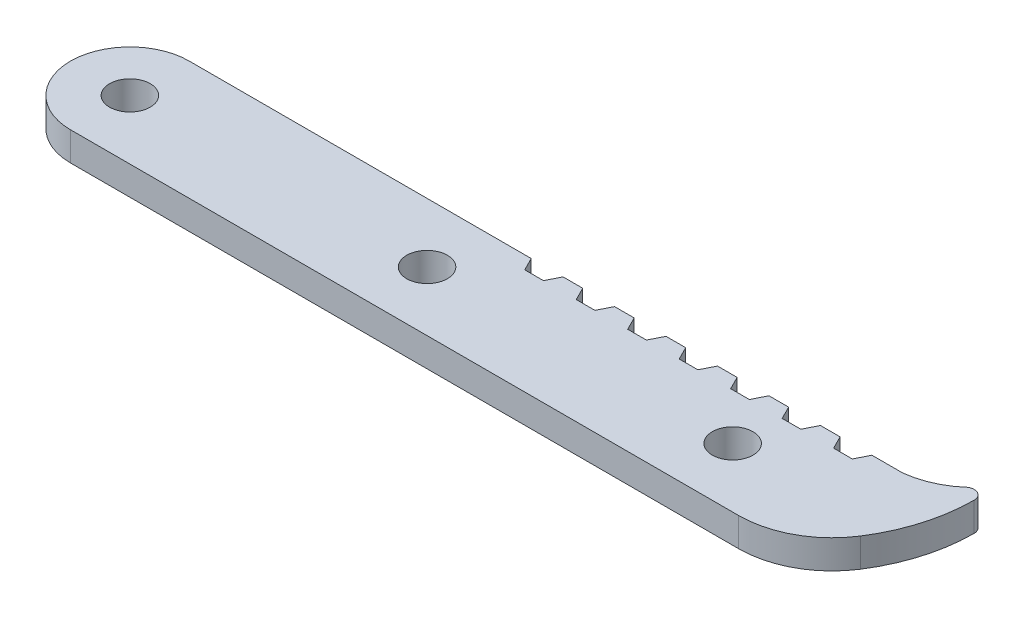
SolidWorks part; units mm, degrees
material "PET"
ref_plane "Front" through (0, 0, 0) normal (0, 0, 1) x (1, 0, 0)
ref_plane "Top" through (0, 0, 0) normal (0, 1, 0) x (1, 0, 0)
ref_plane "Right" through (0, 0, 0) normal (1, 0, 0) x (0, 0, -1)
sketch "Sketch1" plane through (0, 0, 0) normal (0, 1, 0) x (1, 0, 0)
  line L1 (-62.8447, 8.7002) -> (13.3553, 8.7002)
  line L3 (-62.8447, -3.9998) -> (13.3553, -3.9998)
  line L5 (-62.8447, 8.7002) -> (13.3553, -3.9998) construction
  line L6 (-62.8447, -3.9998) -> (13.3553, 8.7002) construction
  arc A0 (-62.8447, 8.7002) -> (-62.8447, -3.9998) centre (-62.8447, 2.3502) ccw
  arc A2 (13.3553, 8.7002) -> (13.3553, -3.9998) centre (13.3553, 2.3502) cw
  point P4 (-24.7447, 2.3502)
  dimension "D1" = 76.2
  dimension "D2" = 12.7
extrude "Boss-Extrude1" add sketch "Sketch1" along normal blind 3.075
sketch "Sketch2" plane through (0, 3.075, 0) normal (0, 1, 0) x (1, 0, 0)
  circle A0 centre (-62.8447, 2.3502) radius 2.175
  circle A1 centre (-31.0947, 2.3502) radius 2.175
  circle A2 centre (1.5553, 2.3502) radius 2.175
  arc A3 (13.3553, -3.9998) -> (13.3553, 8.7002) centre (13.3553, 2.3502) ccw construction
  dimension "D1" = 31.75
  dimension "D2" = 4.35
  dimension "D3" = 4.35
  dimension "D4" = 4.35
  dimension "D5" = 11.8
extrude "Cut-Extrude2" cut sketch "Sketch2" against normal blind 6.35 contours A1 | A0 | A2
sketch "Sketch3" plane through (0, 3.075, 0) normal (0, 1, 0) x (1, 0, 0)
  line L2 (13.3553, 8.7002) -> (13.3553, 2.3502)
  line L7 (19.7053, 2.3502) -> (19.7053, 9.9994)
  line L8 (19.7053, 2.3502) -> (13.3553, 2.3502)
  arc A0 (13.3553, -3.9998) -> (13.3553, 8.7002) centre (13.3553, 2.3502) ccw construction
  arc A2 (19.7053, 9.9994) -> (18.1741, 10.8466) centre (18.7053, 9.9994) ccw
  arc A3 (18.1741, 10.8466) -> (13.3553, 8.7002) centre (12.37, 17.3945) cw
  point P4 (25.0274, 5.3951)
  dimension "D1" = 1
  dimension "D2" = 7.6492
  dimension "D3" = 6.35
  dimension "D5" = 1.75
  dimension "D6" = 8.75
  dimension "D4" = 6.35
extrude "Boss-Extrude2" add sketch "Sketch3" against normal up to vertex (3.075 mm away) up to point (13.3553, 0, -8.7002)
sketch "Sketch4" plane through (0, 3.075, 0) normal (0, 1, 0) x (1, 0, 0)
  line L1 (19.7053, 9.9994) -> (19.7053, -6.0006)
  line L2 (19.7053, -6.0006) -> (9.2053, -6.0006)
  arc A3 (19.7053, 9.9994) -> (9.2053, -6.0006) centre (2.2054, 10.0384) cw
  arc A4 (19.7053, 9.9994) -> (18.1741, 10.8466) centre (18.7053, 9.9994) ccw construction
  dimension "D1" = 16
  dimension "D3" = 17.5
  dimension "D2" = 10.5
extrude "Cut-Extrude3" cut sketch "Sketch4" against normal blind 10
fillet "Fillet1" radius 10 1 edges at (12.6542, 1.5375, 3.9998)
sketch "Sketch5" plane through (0, 3.075, 0) normal (0, 1, 0) x (1, 0, 0)
  line L0 (-4.3147, 8.7002) -> (-0.9147, 8.7002)
  line L1 (13.3553, 8.7002) -> (-62.8447, 8.7002) construction
  line L3 (-9.8147, 8.7002) -> (-9.1147, 7.306)
  line L4 (-9.1147, 7.306) -> (-7.1147, 7.306)
  line L5 (-7.1147, 7.306) -> (-6.4147, 8.7002)
  line L14 (-4.3147, 8.7002) -> (-3.6147, 7.306)
  line L18 (-9.8147, 8.7002) -> (-6.4147, 8.7002)
  line L19 (-3.6147, 7.306) -> (-1.6147, 7.306)
  line L20 (-1.6147, 7.306) -> (-0.9147, 8.7002)
  line L21 (1.1853, 8.7002) -> (4.5853, 8.7002)
  line L22 (1.1853, 8.7002) -> (1.8853, 7.306)
  line L23 (1.8853, 7.306) -> (3.8853, 7.306)
  line L24 (3.8853, 7.306) -> (4.5853, 8.7002)
  line L25 (6.6853, 8.7002) -> (10.0853, 8.7002)
  line L26 (6.6853, 8.7002) -> (7.3853, 7.306)
  line L27 (7.3853, 7.306) -> (9.3853, 7.306)
  line L28 (9.3853, 7.306) -> (10.0853, 8.7002)
  line L29 (-15.3147, 8.7002) -> (-11.9147, 8.7002)
  line L30 (-15.3147, 8.7002) -> (-14.6147, 7.306)
  line L31 (-14.6147, 7.306) -> (-12.6147, 7.306)
  line L32 (-12.6147, 7.306) -> (-11.9147, 8.7002)
  line L33 (-20.8147, 8.7002) -> (-17.4147, 8.7002)
  line L34 (-20.8147, 8.7002) -> (-20.1147, 7.306)
  line L35 (-20.1147, 7.306) -> (-18.1147, 7.306)
  line L36 (-18.1147, 7.306) -> (-17.4147, 8.7002)
  line L37 (-26.3147, 8.7002) -> (-22.9147, 8.7002)
  line L38 (-26.3147, 8.7002) -> (-25.6147, 7.306)
  line L39 (-25.6147, 7.306) -> (-23.6147, 7.306)
  line L40 (-23.6147, 7.306) -> (-22.9147, 8.7002)
  dimension "D1" = 4
  dimension "D2" = 4
  dimension "D3" = 2
  dimension "D4" = 1.56
  dimension "D5" = 1.56
extrude "Cut-Extrude4" cut sketch "Sketch5" against normal blind 10
